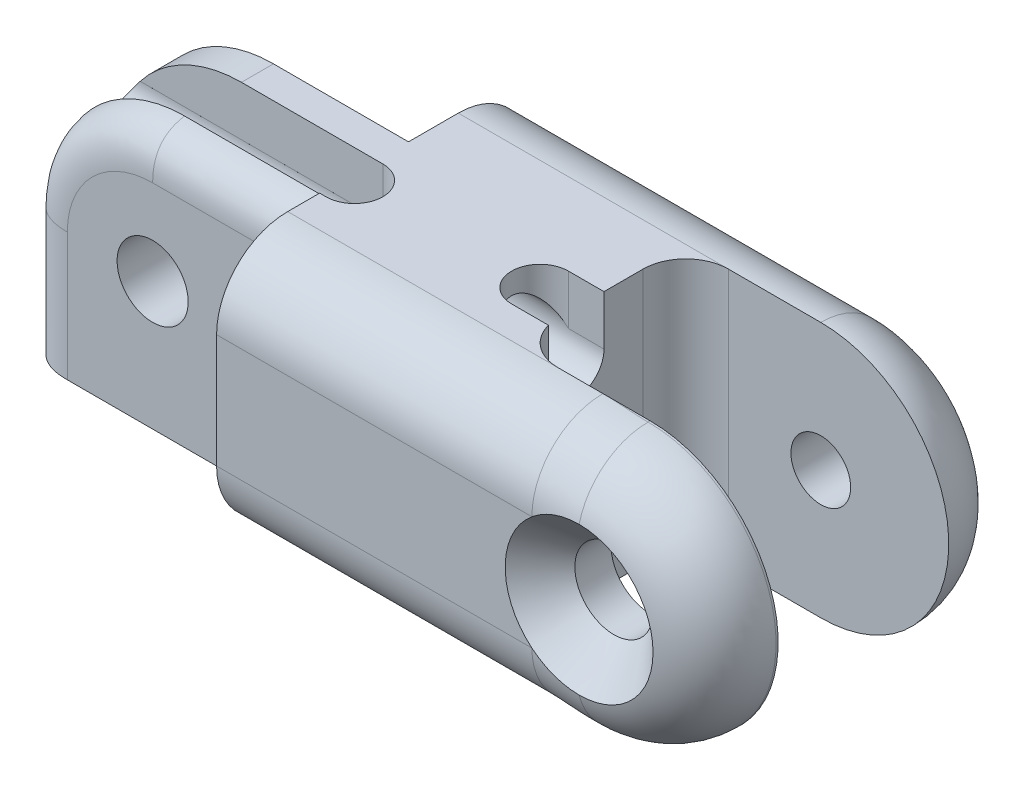
SolidWorks part; units mm, degrees
ref_plane "Front Plane" through (0, 0, 0) normal (0, 0, 1) x (1, 0, 0)
ref_plane "Top Plane" through (0, 0, 0) normal (0, 1, 0) x (1, 0, 0)
ref_plane "Right Plane" through (0, 0, 0) normal (1, 0, 0) x (0, 0, -1)
sketch "Sketch2" plane through (0, 0, 0) normal (0, 1, 0) x (1, 0, 0)
  line L0 (-8, 11) -> (26.5, 11)
  line L1 (26.5, 11) -> (26.5, 6)
  line L2 (26.5, 6) -> (11, 6)
  line L3 (8, 3) -> (8, -3)
  line L4 (11, -6) -> (26.5, -6)
  line L5 (26.5, -6) -> (26.5, -11)
  line L7 (-26.5, -6) -> (-26.5, 2.5)
  line L8 (-49.3622, 0) -> (56.3776, 0) construction
  line L9 (0, 21.2372) -> (0, -19.0689) construction
  line L10 (8, 3) -> (11, 3) construction
  line L11 (11, 3) -> (11, 6) construction
  line L16 (-8, -11) -> (26.5, -11)
  line L18 (-26.5, -6) -> (-8, -6)
  line L19 (-8, -6) -> (-8, -11)
  line L20 (-26.5, 2.5) -> (-8, 2.5)
  line L21 (-8, 2.5) -> (-8, 11)
  arc A0 (11, 6) -> (8, 3) centre (11, 3) ccw
  arc A1 (11, -6) -> (8, -3) centre (11, -3) cw
  point P13 (11, 3)
  dimension "D1" = 53
  dimension "D2" = 22
  dimension "D3" = 5
  dimension "D4" = 18.5
  dimension "D5" = 12
  dimension "D6" = 3
  dimension "D7" = 3
  dimension "D8" = 8.5
  dimension "D9" = 5
  dimension "D10" = 8.5
  dimension "D11" = 18.5
extrude "Boss-Extrude1" add sketch "Sketch2" along normal blind 18
sketch "Sketch5" plane through (0, 0, 11) normal (0, 0, 1) x (1, 0, 0)
  line L0 (-26.5, 9) -> (31.8491, 9) construction
  line L1 (-17.5, 18) -> (-17.5, 0) construction
  line L2 (26.5, 18) -> (26.5, 0) construction
  line L3 (-8, 18) -> (26.5, 18) construction
  line L4 (17.5, 18) -> (17.5, 0) construction
  line L5 (-26.5, 18) -> (-26.5, 0) construction
  line L6 (-26.5, 9) -> (-26.5, 0)
  line L7 (-26.5, 18) -> (-8, 18) construction
  line L8 (-26.5, 0) -> (17.5, 0)
  line L9 (-17.5, 18) -> (17.5, 18)
  arc A0 (-17.5, 18) -> (-26.5, 9) centre (-17.5, 9) ccw
  arc A1 (17.5, 0) -> (17.5, 18) centre (17.5, 9) ccw
  circle A2 centre (-17.5, 9) radius 2.5
  dimension "D2" = 5
  dimension "D1" = 9
extrude "Cut-Extrude1" cut sketch "Sketch5" against normal blind 22 flip side to cut
sketch "Sketch6" plane through (0, 0, 11) normal (0, 0, 1) x (1, 0, 0)
  line L0 (17.5, 0) -> (17.5, 18) construction
  point P4 (17.5, 9)
hole_wizard "CSK for M5 Countersunk Flat Head Screw1" positions "Sketch7" profile "Sketch8" countersink size "M5" standard "DIN" end condition up to next
sketch "Sketch7" plane through (0, 0, 11) normal (0, 0, 1) x (1, 0, 0)
  point P0 (17.5, 9)
sketch "Sketch8" plane through (17.5, 9, 11) normal (1, 0, 0) x (0, -1, 0)
  line L0 (0, 0) -> (0, 5)
  line L1 (0, 5) -> (2.75, 5)
  line L2 (2.75, 5) -> (2.75, 2.45)
  line L3 (2.75, 2.45) -> (5.2, 0)
  line L5 (5.2, 0) -> (0, 0)
  line L6 (-2.75, 2.45) -> (-5.2, 0) construction
  line L11 (0, -6.35) -> (0, 107.95) construction
  dimension "Thru Hole Dia." = 5.5
  dimension "Thru Hole Depth" = 5
  dimension "Near C'Sink Dia." = 10.4
  dimension "Near C'Sink Angle" = 90
hole_wizard "M5 Tapped Hole1" positions "Sketch9" profile "Sketch11" tap size "M5" standard "DIN" end condition through all
sketch "Sketch9" plane through (0, 0, 11) normal (0, 0, 1) x (1, 0, 0)
  point P0 (17.5, 9)
sketch "Sketch11" plane through (17.5, 9, 11) normal (1, 0, 0) x (0, -1, 0)
  line L0 (0, 0) -> (0, 22)
  line L1 (0, 22) -> (2.1, 22)
  line L2 (2.1, 22) -> (2.1, 3.1)
  line L3 (2.1, 3.1) -> (5.2, 0)
  line L5 (5.2, 0) -> (0, 0)
  line L6 (-2.1, 3.1) -> (-5.2, 0) construction
  line L11 (0, -6.35) -> (0, 107.95) construction
  dimension "Thru Tap Drill Dia." = 4.2
  dimension "Thru Tap Drill Depth" = 22
  dimension "Near C'Sink Dia." = 10.4
  dimension "Near C'Sink Angle" = 90
cosmetic thread "Hole Thread1" parameters "D2"=5
fillet "Fillet3" radius 3 3 edges at (-26.5, 4.5, 6) (-12.75, 18, 6) (-23.864, 15.364, 6) conic rho 0.5
sketch "Sketch13" plane through (8, 0, 0) normal (1, 0, 0) x (0, 0, -1)
  line L0 (-1.75, 21.4915) -> (-1.75, -4.5302) construction
  line L1 (-3, 18) -> (3, 18) construction
  circle A0 centre (-1.75, 14.5) radius 2
  dimension "D2" = 4
  dimension "D3" = 3.5
  dimension "D1" = 1.75
extrude "Cut-Extrude2" cut sketch "Sketch13" against normal through all both and the other way through all
sketch "Sketch14" plane through (0, 18, 0) normal (0, 1, 0) x (1, 0, 0)
  line L0 (-24.6236, 0.2504) -> (-7.5557, 0.2504)
  line L1 (-24.5557, -3.75) -> (-7.5557, -3.75)
  line L3 (-24.5557, -3.75) -> (-24.6236, 0.2504)
  arc A0 (-7.5557, -3.75) -> (-7.5557, 0.2504) centre (-7.5557, -1.7498) ccw
  spline S1 degree 3 poles (-23.0797, -3) (-22.9473, -2.8693) (-22.8242, -2.7233) (-22.6669, -2.4679) (-22.62, -2.3776) (-22.5431, -2.1872) (-22.5127, -2.0851) (-22.4764, -1.8774) (-22.4703, -1.7698) (-22.4841, -1.5572) (-22.5036, -1.4537) (-22.5944, -1.1509) (-22.6934, -0.9724) (-22.9222, -0.6565) (-23.0506, -0.5207) (-23.3219, -0.2789) (-23.4619, -0.1762) (-23.8834, 0.0849) (-24.1717, 0.1991) (-24.5706, 0.2557) (-24.7006, 0.2556) (-24.9459, 0.209) (-25.0594, 0.1634) (-25.269, 0.0188) (-25.3624, -0.0793) (-25.5226, -0.3256) (-25.5911, -0.4779) (-25.6703, -0.7331) (-25.6932, -0.8231) (-25.7322, -1.0133) (-25.7481, -1.1133) (-25.7724, -1.3157) (-25.781, -1.419) (-25.7912, -1.6301) (-25.7926, -1.7379) (-25.7863, -2.055) (-25.7677, -2.2665) (-25.7021, -2.6575) (-25.6546, -2.8399) (-25.5922, -3) knots 0 0 0 0 0.0625 0.0625 0.09375 0.09375 0.125 0.125 0.15625 0.15625 0.1875 0.1875 0.25 0.25 0.3125 0.3125 0.375 0.375 0.5 0.5 0.5625 0.5625 0.625 0.625 0.6875 0.6875 0.75 0.75 0.78125 0.78125 0.8125 0.8125 0.84375 0.84375 0.875 0.875 0.9375 0.9375 1 1 1 1 construction
  spline S2 degree 3 poles (-25.5922, -3) (-25.5381, -3.1387) (-25.4701, -3.2552) (-25.3108, -3.4526) (-25.2195, -3.5323) (-25.0254, -3.6532) (-24.9205, -3.6957) (-24.705, -3.7461) (-24.594, -3.7546) (-24.2507, -3.7337) (-24.0173, -3.6588) (-23.5422, -3.4019) (-23.3092, -3.2263) (-23.0797, -3) knots 0 0 0 0 0.125 0.125 0.25 0.25 0.375 0.375 0.5 0.5 0.75 0.75 1 1 1 1 construction
  dimension "D2" = 2.0002
  dimension "D1" = 17
extrude "Cut-Extrude3" cut sketch "Sketch14" against normal blind 3.5
sketch "Sketch15" plane through (0, 18, 0) normal (0, 1, 0) x (1, 0, 0)
sketch "Sketch16" plane through (0, 18, 0) normal (0, 1, 0) x (1, 0, 0)
  line L0 (-8.0769, -1.75) -> (29.6251, -1.75) construction
  line L1 (5.5, 0.25) -> (19.0559, 0.25)
  line L3 (5.5, -3.75) -> (19.0559, -3.75)
  line L4 (19.0559, 0.25) -> (19.0559, -3.75)
  line L5 (8, -3) -> (8, 3) construction
  arc A0 (5.5, 0.25) -> (5.5, -3.75) centre (5.5, -1.75) ccw
  dimension "D2" = 4
  dimension "D1" = 1.75
  dimension "D3" = 2.5
extrude "Cut-Extrude4" cut sketch "Sketch16" against normal blind 3.5
fillet "Fillet4" radius 5 5 edges at (4.75, 0, -11) (26.5, 9, -11) (4.75, 0, 11) (4.75, 18, -11) (4.75, 18, 11)
